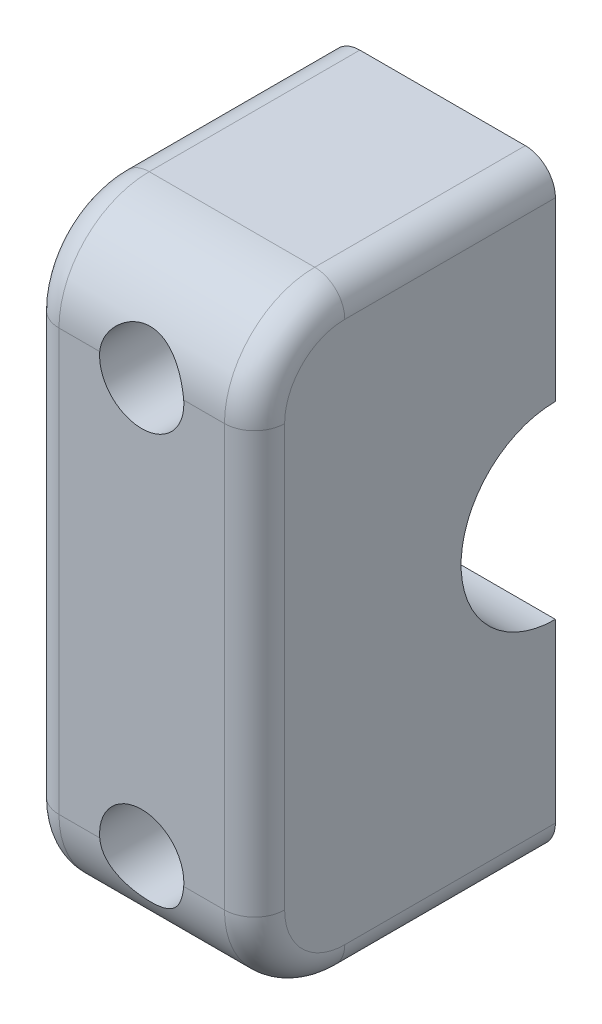
SolidWorks part; units mm, degrees
ref_plane "Front Plane" through (0, 0, 0) normal (0, 0, 1) x (1, 0, 0)
ref_plane "Top Plane" through (0, 0, 0) normal (0, 1, 0) x (1, 0, 0)
ref_plane "Right Plane" through (0, 0, 0) normal (1, 0, 0) x (0, 0, -1)
sketch "Sketch2" plane through (0, 0, 0) normal (0, 0, 1) x (1, 0, 0)
  line L0 (14.1609, -51.7716) -> (14.1609, -26.3716)
  line L1 (14.1609, -51.7716) -> (4.6359, -51.7716)
  line L2 (14.1609, -26.3716) -> (4.6359, -26.3716)
  line L3 (4.6359, -51.7716) -> (4.6359, -26.3716)
extrude "Boss-Extrude1" add sketch "Sketch2" along normal blind 12.7
fillet "Fillet1" radius 1.27 6 edges at (4.6359, -39.0716, 12.7) (14.1609, -39.0716, 12.7) (4.6359, -51.7716, 6.35) (4.6359, -26.3716, 6.35) (14.1609, -26.3716, 6.35) (14.1609, -51.7716, 6.35)
fillet "Fillet2" radius 3.81 6 edges at (9.3984, -26.3716, 12.7) (9.3984, -51.7716, 12.7) (13.7889, -51.3996, 12.328) (13.7889, -26.7435, 12.328) (5.0079, -51.3996, 12.328) (5.0079, -26.7435, 12.328)
sketch "Sketch14" plane through (4.6359, 0, 0) normal (-1, 0, 0) x (0, 0, 1)
  circle A0 centre (0, -39.0716) radius 6.35 construction
  circle A1 centre (0, -39.0716) radius 6.35
sketch "Sketch15" plane through (4.6359, 0, 0) normal (-1, 0, 0) x (0, 0, 1)
  circle A0 centre (0, -39.0716) radius 3.9818 construction
  circle A1 centre (0, -39.0716) radius 3.9818
extrude "Cut-Extrude12" cut sketch "Sketch15" against normal through all
extrude "Cut-Extrude13" cut sketch "Sketch14" against normal blind 4.064
sketch "Sketch17" plane through (0, 0, 12.7) normal (0, 0, 1) x (1, 0, 0)
  circle A0 centre (9.3984, -47.8092) radius 1.778 construction
  circle A1 centre (9.3984, -47.8092) radius 1.778
  circle A2 centre (9.3984, -30.334) radius 1.778 construction
  circle A3 centre (9.3984, -30.334) radius 1.778
extrude "Cut-Extrude14" cut sketch "Sketch17" against normal through all
